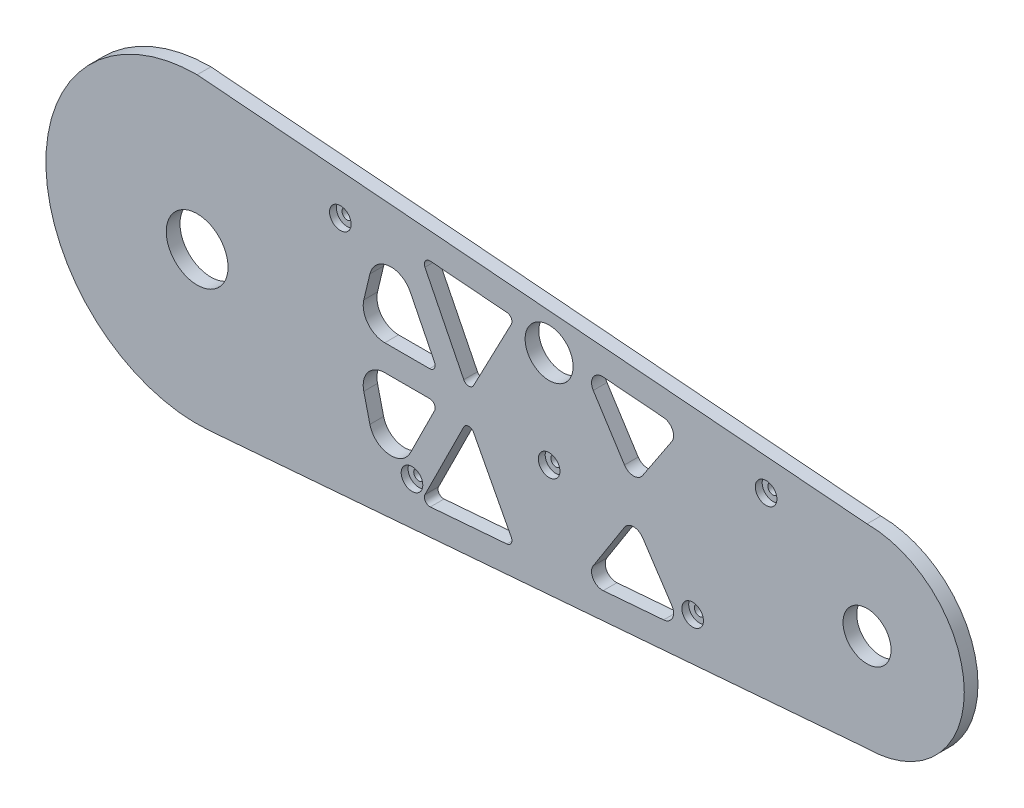
SolidWorks part; units mm, degrees
other "Marca1"
sketch "Croquis3" plane through (-70, -70, 6.35) normal (0, 0, 1) x (1, 0, 0)
material "6061-O (SS)"
ref_plane "Front Plane" through (0, 0, 0) normal (0, 0, 1) x (1, 0, 0)
ref_plane "Top Plane" through (0, 0, 0) normal (0, 1, 0) x (1, 0, 0)
ref_plane "Right Plane" through (0, 0, 0) normal (1, 0, 0) x (0, 0, -1)
sketch "Sketch1" plane through (0, 0, 0) normal (0, 0, 1) x (1, 0, 0)
  line L0 (0, 70) -> (310, 45)
  line L1 (5.1714, -69.8087) -> (310, -45)
  line L2 (0, 0) -> (310, 0) construction
  line L3 (107.899, 49.2595) -> (143.3142, 46.4034)
  line L4 (78.877, 6) -> (107.5747, 6)
  line L5 (219.6238, 32.8105) -> (206.1309, 12.4175)
  line L6 (197.7459, 12.4871) -> (183.2969, 35.1335)
  line L7 (162.8785, 6) -> (162.8785, -6) construction
  line L8 (258.6323, 64.5867) -> (258.6323, 39.5867) construction
  line L9 (145.3724, 42.6674) -> (127.93, 9.4277)
  line L10 (123.3779, 9.4761) -> (105.405, 45.5719)
  line L11 (103.3877, 49.6233) -> (42.0027, 49.6233) construction
  line L12 (187.9139, 42.8067) -> (215.8558, 40.5533)
  line L13 (162.8785, 44.8257) -> (162.8785, 6) construction
  line L14 (67.1248, 64.5867) -> (162.8785, 40) construction
  line L15 (201.8849, 6) -> (201.8849, 41.68) construction
  line L16 (125.6066, 5) -> (125.6066, 47.8315) construction
  line L17 (98.6184, 32.2793) -> (109.8632, 9.6959)
  line L18 (125.6066, -5) -> (125.6066, -47.8315) construction
  line L19 (201.8849, -6) -> (201.8849, -41.68) construction
  line L20 (162.8785, -44.8257) -> (162.8785, -6) construction
  line L21 (103.3877, -49.6233) -> (42.0027, -49.6233) construction
  line L22 (98.6184, -32.2793) -> (109.8632, -9.6959)
  line L23 (67.1248, 64.5867) -> (409.6974, 64.5867) construction
  line L24 (187.9139, -42.8067) -> (215.8558, -40.5533)
  line L25 (123.3779, -9.4761) -> (105.405, -45.5719)
  line L26 (145.3724, -42.6674) -> (127.93, -9.4277)
  line L27 (162.8785, 0) -> (258.6323, 64.5867) construction
  line L28 (67.1248, 64.5867) -> (67.1248, 39.5867) construction
  line L29 (197.7459, -12.4871) -> (183.2969, -35.1335)
  line L30 (219.6238, -32.8105) -> (206.1309, -12.4175)
  line L31 (78.877, -6) -> (107.5747, -6)
  line L32 (107.899, -49.2595) -> (143.3142, -46.4034)
  line L33 (0, -6.35) -> (0, 6.35) construction
  line L34 (67.1248, 39.5867) -> (162.8785, 40) construction
  line L35 (162.8785, 40) -> (68.3705, 24.1395) construction
  line L36 (79.9417, 30.1512) -> (74.6977, 8.2553)
  line L37 (79.9417, -30.1512) -> (74.6977, -8.2553)
  arc A0 (74.6977, 8.2553) -> (78.877, 6) centre (78.877, 11) ccw
  arc A1 (310, -45) -> (310, 45) centre (310, 0) ccw
  circle A2 centre (0, 0) radius 14.2938
  circle A3 centre (310, 0) radius 11.116
  arc A4 (79.9417, 30.1512) -> (98.6184, 32.2793) centre (89.6667, 27.822) cw
  arc A5 (79.9417, -30.1512) -> (98.6184, -32.2793) centre (89.6667, -27.822) ccw
  arc A6 (0, 70) -> (5.1714, -69.8087) centre (0, 0) ccw
  arc A7 (187.9139, 42.8067) -> (183.2969, 35.1335) centre (187.512, 37.8229) ccw
  arc A8 (219.6238, 32.8105) -> (215.8558, 40.5533) centre (215.4539, 35.5695) ccw
  arc A9 (206.1309, 12.4175) -> (197.7459, 12.4871) centre (201.961, 15.1765) cw
  circle A10 centre (162.8785, 40) radius 11.1125
  arc A13 (107.5747, 6) -> (109.8632, 9.6959) centre (107.5747, 8.5564) ccw
  arc A14 (123.3779, 9.4761) -> (127.93, 9.4277) centre (125.6663, 10.6155) ccw
  arc A15 (145.3724, 42.6674) -> (143.3142, 46.4034) centre (143.1088, 43.8553) ccw
  arc A16 (107.899, 49.2595) -> (105.405, 45.5719) centre (107.6935, 46.7114) ccw
  arc A17 (107.899, -49.2595) -> (105.405, -45.5719) centre (107.6935, -46.7114) cw
  arc A18 (145.3724, -42.6674) -> (143.3142, -46.4034) centre (143.1088, -43.8553) cw
  arc A19 (123.3779, -9.4761) -> (127.93, -9.4277) centre (125.6663, -10.6155) cw
  arc A20 (107.5747, -6) -> (109.8632, -9.6959) centre (107.5747, -8.5564) cw
  arc A24 (206.1309, -12.4175) -> (197.7459, -12.4871) centre (201.961, -15.1765) ccw
  arc A25 (219.6238, -32.8105) -> (215.8558, -40.5533) centre (215.4539, -35.5695) cw
  arc A26 (187.9139, -42.8067) -> (183.2969, -35.1335) centre (187.512, -37.8229) cw
  arc A29 (74.6977, -8.2553) -> (78.877, -6) centre (78.877, -11) cw
  point P31 (177.8851, 43.6155)
  point P42 (187.6504, 6)
  point P44 (86.3517, 56.9152)
  point P45 (138.1067, 6)
  point P79 (86.3517, -56.9152)
  point P100 (138.1067, -6)
  point P101 (187.6504, -6)
  point P102 (177.8851, -43.6155)
  point P104 (0, 0)
  point P114 (310, 0)
  point P119 (0.2114, 0.3175)
  dimension "D2" = 45
  dimension "D3" = 12.7
  dimension "D4" = 22.232
  dimension "D6" = 12
  dimension "D11" = 5
  dimension "D12" = 70
  dimension "D13" = 25
  dimension "D8" = 5
  dimension "D14" = 12
  dimension "D15" = 25
  dimension "D16" = 310
  dimension "D17" = 22.225
  dimension "D5" = 28.5877
  dimension "D19" = 10
  dimension "D20" = 10
  dimension "D7" = 6
  dimension "D9" = 9.279
  dimension "D10" = 34
  dimension "D18" = 40
extrude "Boss-Extrude1" add sketch "Sketch1" along normal blind 6.35
sketch "Sketch2" plane through (0, 0, 6.35) normal (0, 0, 1) x (1, 0, 0)
  line L0 (263.0927, 39.4927) -> (-0.4655, 64.9983)
  line L1 (4.6885, -64.8307) -> (263.1366, -39.5384)
  arc A0 (-0.4655, 64.9983) -> (4.6885, -64.8307) centre (0, 0) ccw
  arc A1 (263.1366, -39.5384) -> (270.3186, -23.7999) centre (262.1626, -29.5859) ccw
  circle A2 centre (0, 0) radius 40
  arc A3 (270.292, 23.7623) -> (270.3186, -23.7999) centre (303.867, 0) ccw
  arc A4 (270.292, 23.7623) -> (263.0927, 39.4927) centre (262.1295, 29.5392) ccw
  dimension "D1" = 10
  dimension "D2" = 41.133
  dimension "D3" = 65
ref_plane "Plane1" through (0, 0, 10) normal (0, 0, 1) x (1, 0, 0)
sketch "Croquis1" plane through (0, 0, 6.35) normal (0, 0, 1) x (1, 0, 0)
  line L0 (99.4174, -42.273) -> (229.2992, -31.7024) construction
  line L1 (5.1714, -69.8087) -> (310, -45) construction
  circle A1 centre (99.4174, -42.273) radius 2.3813
  circle A2 centre (229.2992, -31.7024) radius 2.3812
  point P20 (0, 0)
  dimension "D5" = 4.7625
  dimension "D1" = 4.7625
  dimension "D2" = 19.8
extrude "Cortar-Extruir1" cut sketch "Croquis1" against normal blind 50
sketch "Croquis4" plane through (0, 0, 0) normal (0, 0, -1) x (-1, 0, 0)
  circle A0 centre (-229.2992, -31.7024) radius 5
  circle A1 centre (-99.4174, -42.273) radius 5
  dimension "D1" = 10
sketch "Croquis5" plane through (0, 0, 0) normal (0, 0, -1) x (-1, 0, 0)
  line L0 (-162.8785, 40) -> (-162.8785, -35.6506) construction
  line L1 (-193.2674, -35.6506) -> (-132.4897, -35.6506) construction
  circle A0 centre (-162.8785, 0) radius 5
  point P6 (-162.8785, -35.6506)
  dimension "D2" = 10
  dimension "D1" = 40
sketch "Croquis6" plane through (0, 0, 0) normal (0, 0, -1) x (-1, 0, 0)
  circle A0 centre (-162.8785, -5) radius 2.3813
  dimension "D1" = 4.7625
extrude "Cortar-Extruir4" cut sketch "Croquis6" against normal blind 10
sketch "Croquis7" plane through (0, 0, 0) normal (0, 0, -1) x (-1, 0, 0)
  line L0 (-229.2992, -31.7024) -> (-99.4174, -42.273) construction
  line L1 (-99.4174, -42.273) -> (-66.2632, 45.6861) construction
  line L2 (-229.2992, -31.7024) -> (-263.2934, 34.0273) construction
  circle A0 centre (-66.2632, 45.6861) radius 2.3812
  circle A1 centre (-263.2934, 34.0273) radius 2.3813
  dimension "D5" = 4.7625
  dimension "D1" = 94
  dimension "D2" = 106
  dimension "D3" = 74
  dimension "D4" = 238
extrude "Cortar-Extruir5" cut sketch "Croquis7" against normal blind 10
sketch "Croquis8" plane through (0, 0, 0) normal (0, 0, -1) x (-1, 0, 0)
  circle A0 centre (-263.2934, 34.0273) radius 5
  circle A1 centre (-66.2632, 45.6861) radius 5
  dimension "D1" = 10
  dimension "D2" = 10
sketch "Croquis9" plane through (0, 0, 6.35) normal (0, 0, 1) x (1, 0, 0)
  circle A0 centre (66.2632, 45.6861) radius 5
  circle A1 centre (162.8785, -5) radius 5
  circle A2 centre (99.4174, -42.273) radius 5
  circle A3 centre (229.2992, -31.7024) radius 5
  circle A4 centre (263.2934, 34.0273) radius 5
  dimension "D1" = 10
extrude "Cortar-Extruir6" cut sketch "Croquis9" against normal blind 3.18
fillet "Redondeo1" radius 10 2 edges at (74.6977, 8.2553, 3.175) (74.6977, -8.2553, 3.175)
